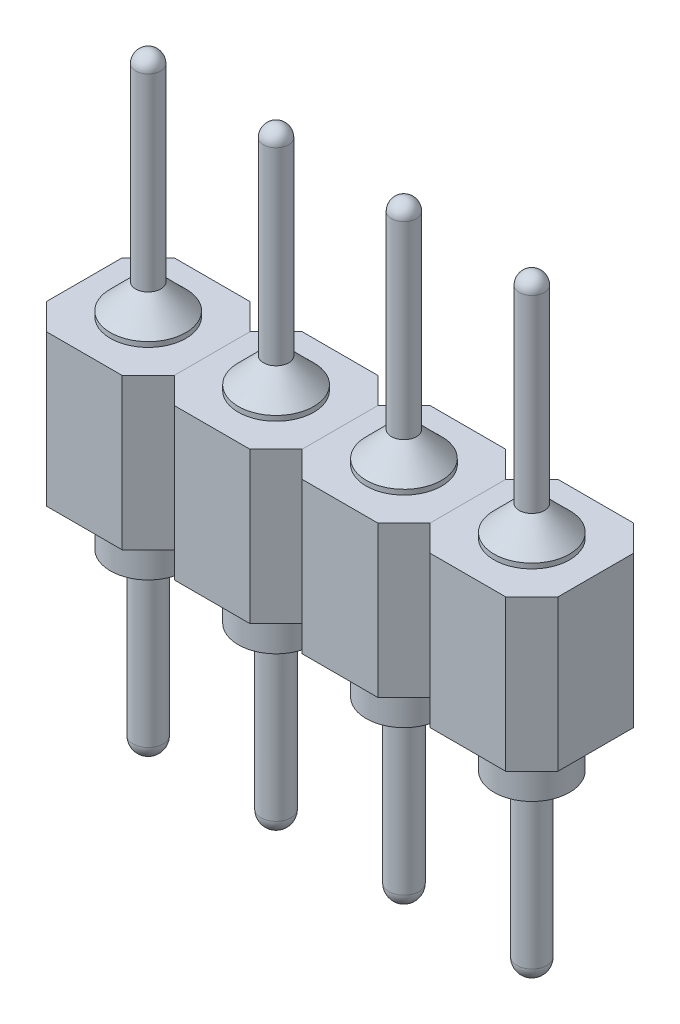
SolidWorks part; units mm, degrees
ref_plane "Спереди" through (0, 0, 0) normal (0, 0, 1) x (1, 0, 0)
ref_plane "Сверху" through (0, 0, 0) normal (0, 1, 0) x (1, 0, 0)
ref_plane "Справа" through (0, 0, 0) normal (1, 0, 0) x (0, 0, -1)
other "Configuration Table"
sketch "Эскиз2" plane through (0, 0, 0) normal (0, 0, 1) x (1, 0, 0)
  line L0 (0, 12.1) -> (0, 0) construction
  line L1 (0, 0) -> (0, 12.1)
  line L2 (0.3, 0.3) -> (0.3, 3.5)
  line L3 (0.3, 3.5) -> (0.75, 3.5)
  line L4 (0.75, 3.5) -> (0.75, 7.6)
  line L5 (0.25, 11.85) -> (0.25, 8.1)
  line L6 (0.25, 8.1) -> (0.75, 7.6)
  circle A0 centre (0, 11.85) radius 0.25
  circle A1 centre (0, 0.3) radius 0.3
  dimension "D1" = 0.5
  dimension "D2" = 0.6
  dimension "D3" = 4
  dimension "D4" = 0.5
  dimension "D5" = 4.1
  dimension "D6" = 3.5
  dimension "D7" = 0.75
revolve "Повернуть1" add sketch "Эскиз2" angle 360 about L1
sketch "Эскиз3" plane through (0, 3.5, 0) normal (0, -1, 0) x (1, 0, 0)
  line L0 (0, 1.27) -> (0, -1.27) construction
  line L1 (-0.75, 1.27) -> (0.75, 1.27)
  line L2 (-1.27, 0.75) -> (-1.27, -0.75)
  line L3 (-0.75, -1.27) -> (0.75, -1.27)
  line L4 (1.27, 0.75) -> (1.27, -0.75)
  line L5 (-1.27, 0.75) -> (-0.75, 1.27)
  line L6 (0.75, 1.27) -> (1.27, 0.75)
  line L7 (0.75, -1.27) -> (1.27, -0.75)
  line L8 (-1.27, -0.75) -> (-0.75, -1.27)
  circle A0 centre (0, 0) radius 0.75
  point P0 (-1.27, 1.27)
  point P1 (1.27, -1.27)
  point P2 (-1.27, -1.27)
  point P3 (1.27, 1.27)
  dimension "D2" = 1.5
  dimension "D1" = 2.54
  dimension "D3" = 2.54
extrude "Бобышка-Вытянуть1" add sketch "Эскиз3" against normal blind 3 from offset 1 separate body offset against normal yes
pattern_linear "Линейный массив1" count 4 spacing 2.54 along (-1, 0, 0) of bodies 103 104
